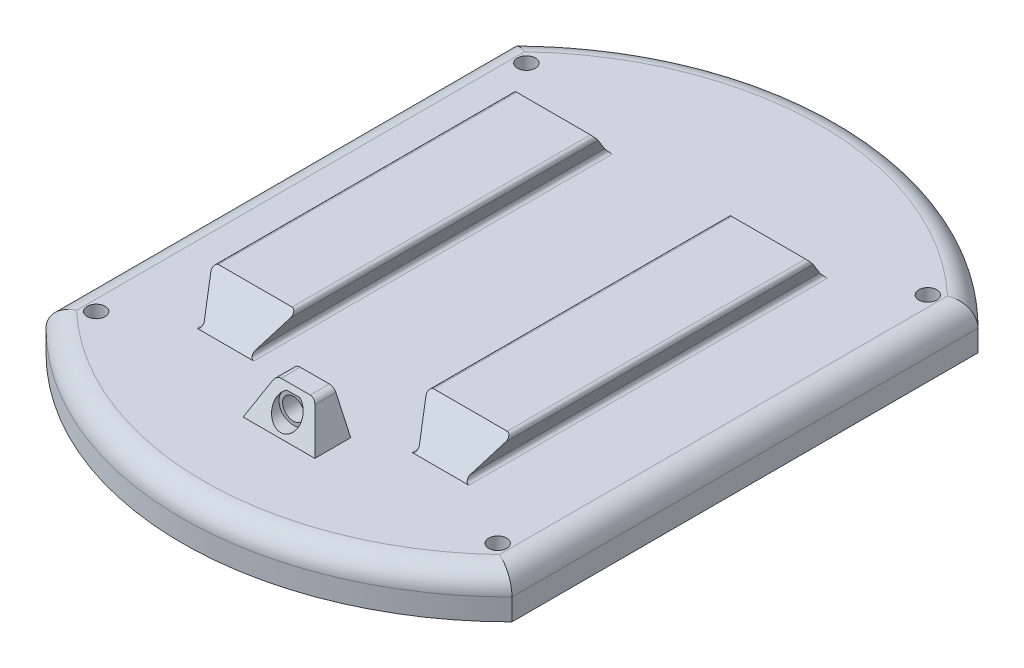
SolidWorks part; units mm, degrees
ref_plane "Спереди" through (0, 0, 0) normal (0, 0, 1) x (1, 0, 0)
ref_plane "Сверху" through (0, 0, 0) normal (0, 1, 0) x (1, 0, 0)
ref_plane "Справа" through (0, 0, 0) normal (1, 0, 0) x (0, 0, -1)
sketch "Эскиз1" plane through (0, 0, 0) normal (0, 1, 0) x (1, 0, 0)
  line L2 (0, -1000) -> (0, 49000) construction
  line L9 (-32.5, -32.5) -> (32.5, -32.5)
  line L10 (-32.5, -32.5) -> (-32.5, 32.5)
  line L11 (-32.5, 32.5) -> (32.5, 32.5)
  line L12 (32.5, -32.5) -> (32.5, 32.5)
  line L13 (-32.5, -32.5) -> (32.5, 32.5) construction
  line L14 (-32.5, 32.5) -> (32.5, -32.5) construction
  arc A5 (32.5, 32.5) -> (-32.5, 32.5) centre (0, 0.1296) ccw
  arc A6 (-32.5, -32.5) -> (32.5, -32.5) centre (0, -0.1296) ccw
  point P17 (0, 0)
  point P26 (0, 46)
  point P28 (0, -46)
  dimension "D6" = 65
  dimension "D7" = 92
extrude "Бобышка-Вытянуть1" add sketch "Эскиз1" along normal blind 6 contours L9 L12 L11 L10 | L11 A5 | L9 A6 | L9 | L9 | L11 | L11 | L11 | L11 | L9 | L9 region at (0, 0, 0) region at (0, 0, 37.9745) region at (0, 0, -37.9745)
sketch "Эскиз2" plane through (0, 0, 0) normal (0, -1, 0) x (1, 0, 0)
  line L0 (-25.75, 31.299) -> (-28, 32.5981)
  line L1 (28, 27.4019) -> (30.25, 28.701)
  line L2 (30.25, 28.701) -> (30.25, 31.299)
  line L3 (30.25, 31.299) -> (28, 32.5981)
  line L4 (28, 32.5981) -> (25.75, 31.299)
  line L5 (25.75, 31.299) -> (25.75, 28.701)
  line L6 (25.75, 28.701) -> (28, 27.4019)
  line L7 (-28, 32.5981) -> (-30.25, 31.299)
  line L8 (-30.25, 31.299) -> (-30.25, 28.701)
  line L9 (-30.25, 28.701) -> (-28, 27.4019)
  line L10 (-28, 27.4019) -> (-25.75, 28.701)
  line L11 (-25.75, 28.701) -> (-25.75, 31.299)
  line L12 (-25.75, -28.701) -> (-28, -27.4019)
  line L13 (-28, -27.4019) -> (-30.25, -28.701)
  line L14 (-30.25, -28.701) -> (-30.25, -31.299)
  line L15 (-30.25, -31.299) -> (-28, -32.5981)
  line L16 (-28, -32.5981) -> (-25.75, -31.299)
  line L17 (-25.75, -31.299) -> (-25.75, -28.701)
  line L18 (30.25, -28.701) -> (28, -27.4019)
  line L19 (28, -27.4019) -> (25.75, -28.701)
  line L20 (25.75, -28.701) -> (25.75, -31.299)
  line L21 (25.75, -31.299) -> (28, -32.5981)
  line L22 (28, -32.5981) -> (30.25, -31.299)
  line L23 (30.25, -31.299) -> (30.25, -28.701)
  circle A0 centre (28, 30) radius 2.25 construction
  circle A1 centre (-28, -30) radius 2.5981
  dimension "D1" = 4.5
  dimension "D4" = 28
  dimension "D5" = 30
  dimension "D6" = 28
  dimension "D7" = 30
  dimension "D2" = 2
  dimension "D3" = 2
extrude "Вырез-Вытянуть1" cut sketch "Эскиз2" against normal blind 3 contours L22 L23 L18 L19 L20 L21 | L5 L6 L1 L2 L3 L4 | L10 L11 L0 L7 L8 L9 | L16 L17 L12 L13 L14 L15 | L12 L13 L14 L15 L16 L17 region at (-28, 0, 30) region at (28, 0, 30) region at (-28, 0, -30) region at (28, 0, -30)
sketch "Эскиз3" plane through (0, 6, 0) normal (0, 1, 0) x (1, 0, 0)
  line L0 (-22.5, 28.0659) -> (-22.5, -28.0659)
  line L1 (22.5, -28.0659) -> (22.5, 28.0659)
  line L2 (-32.5, 32.5) -> (-32.5, -32.5)
  line L3 (32.5, -32.5) -> (32.5, 32.5)
  line L4 (-32.5, 32.5) -> (-32.5, -32.5)
  line L5 (32.5, -32.5) -> (32.5, 32.5)
  arc A0 (22.5, 28.0659) -> (-22.5, 28.0659) centre (0, 0.1296) ccw
  arc A1 (-22.5, -28.0659) -> (22.5, -28.0659) centre (0, -0.1296) ccw
  arc A2 (-32.5, -32.5) -> (32.5, -32.5) centre (0, -0.1296) ccw
  arc A3 (32.5, 32.5) -> (-32.5, 32.5) centre (0, 0.1296) ccw
  arc A4 (-32.5, -32.5) -> (32.5, -32.5) centre (0, -0.1296) ccw
  arc A5 (32.5, 32.5) -> (-32.5, 32.5) centre (0, 0.1296) ccw
  dimension "D2" = 10
  dimension "D1" = 0
sketch "Эскиз4" plane through (0, 3, 0) normal (0, -1, 0) x (1, 0, 0)
  line L0 (28, 32.5981) -> (28, 27.4019) construction
  line L1 (28, 27.4019) -> (30.25, 28.701) construction
  line L2 (-32.5, 32.5) -> (-32.5, -32.5)
  line L3 (32.5, -32.5) -> (32.5, 32.5)
  line L4 (-32.5, 32.5) -> (-32.5, -32.5)
  line L5 (32.5, -32.5) -> (32.5, 32.5)
  line L6 (25.75, 28.701) -> (30.25, 31.299) construction
  line L8 (-25.75, -31.299) -> (-25.75, -28.701) construction
  line L9 (-25.75, -30) -> (-28, -30)
  circle A0 centre (28, 30) radius 1.25
  circle A1 centre (-28, 30) radius 1.25
  arc A2 (-32.5, -32.5) -> (32.5, -32.5) centre (0, -0.1296) ccw
  arc A3 (32.5, 32.5) -> (-32.5, 32.5) centre (0, 0.1296) ccw
  arc A4 (-32.5, -32.5) -> (32.5, -32.5) centre (0, -0.1296) ccw
  arc A5 (32.5, 32.5) -> (-32.5, 32.5) centre (0, 0.1296) ccw
  circle A6 centre (-28, -30) radius 1.25
  circle A7 centre (28, -30) radius 1.25
  dimension "D2" = 2.5
  dimension "D1" = 0
  dimension "D3" = 2
  dimension "D4" = 2
extrude "Вырез-Вытянуть3" cut sketch "Эскиз4" against normal through all contours A0 | A1 | A7 | A6 region at (28, 3, 30) region at (-28, 3, 30) region at (-29.2146, 3, -30) region at (28, 3, -30)
sketch "Эскиз5" plane through (0, 0, 0) normal (0, 0, 1) x (1, 0, 0)
  line L0 (0, -1000) -> (0, 49000) construction
  line L1 (9, 11) -> (21, 11)
  line L2 (21, 11) -> (18.1132, 6)
  line L3 (9, 11) -> (11.8868, 6)
  line L4 (-32.5, 0) -> (32.5, 0)
  line L5 (-32.5, 6) -> (-32.5, 0)
  line L6 (32.5, 6) -> (-32.5, 6)
  line L7 (32.5, 0) -> (32.5, 6)
  line L8 (-32.5, 0) -> (32.5, 0)
  line L9 (-32.5, 6) -> (-32.5, 0)
  line L10 (32.5, 6) -> (-32.5, 6)
  line L11 (32.5, 0) -> (32.5, 6)
  line L12 (15, 11) -> (15, 6) construction
  line L13 (-9, 11) -> (-11.8868, 6)
  line L14 (-15, 11) -> (-15, 6) construction
  line L15 (-9, 11) -> (-21, 11)
  line L16 (-21, 11) -> (-18.1132, 6)
  point P13 (15, 8.5)
  dimension "D2" = 60
  dimension "D3" = 5
  dimension "D4" = 12
  dimension "D5" = 15
  dimension "D1" = 0
extrude "Бобышка-Вытянуть2" add sketch "Эскиз5" along normal mid plane 50 contours L15 L16 L10 L13 | L10 L2 L1 L3 region at (15, 8.764, 0) region at (-15, 8.764, 0)
draft "Уклон1" type of draft neutral plane draft angle 40 faces to draft 4 face at (15, 8.5, -25) face at (15, 8.5, 25) face at (-15, 8.5, -25) face at (-15, 8.5, 25) neutral plane through (0, 6, 0) neutral plane normal (0, 1, 0) parameters "D1"=40
fillet "Скругление1" radius 0.5 8 edges at (18.1132, 6, 0) (21, 11, 0) (9, 11, 0) (11.8868, 6, 0) (-11.8868, 6, 0) (-9, 11, 0) (-21, 11, 0) (-18.1132, 6, 0)
sketch "Эскиз6" plane through (0, 6, 0) normal (0, 1, 0) x (1, 0, 0)
  line L1 (-5, -32.5) -> (5, -32.5)
  line L2 (-5, -32.5) -> (-5, -27.5)
  line L3 (-5, -27.5) -> (5, -27.5)
  line L4 (5, -32.5) -> (5, -27.5)
  line L5 (-5, -32.5) -> (5, -27.5) construction
  line L6 (-5, -27.5) -> (5, -32.5) construction
  point P0 (0, -30)
  dimension "D1" = 10
  dimension "D2" = 5
  dimension "D3" = 30
extrude "Бобышка-Вытянуть3" add sketch "Эскиз6" along normal blind 5
draft "Уклон3" type of draft neutral plane draft angle 25 faces to draft 2 face at (5, 8.5, 30) face at (-5, 8.5, 30) neutral plane through (0, 6, 0) neutral plane normal (0, 1, 0) parameters "D1"=25
fillet "Скругление2" radius 1 2 edges at (2.6685, 11, 30) (-2.6685, 11, 30)
sketch "Эскиз7" plane through (0, 0, 32.5) normal (0, 0, 1) x (1, 0, 0)
  line L0 (-2.0314, 11) -> (2.0314, 11) construction
  circle A0 centre (0, 8.5) radius 1.5
  dimension "D1" = 3
  dimension "D2" = 2.5
extrude "Вырез-Вытянуть4" cut sketch "Эскиз7" against normal blind 5
sketch "Эскиз8" plane through (0, 0, 32.5) normal (0, 0, 1) x (1, 0, 0)
  circle A0 centre (0, 8.5) radius 1.5 construction
  circle A1 centre (0, 8.5) radius 1.5
  circle A2 centre (0, 8.5) radius 2
  dimension "D1" = 4
extrude "Вырез-Вытянуть5" cut sketch "Эскиз8" against normal blind 2
draft "Уклон5" type of draft neutral plane draft angle 25 faces to draft 1 face at (2, 8.5, 32.5) neutral plane through (0, 6, 0) neutral plane normal (0, 1, 0) parameters "D1"=25
fillet "Скругление3" radius 3 4 edges at (0, 6, 46) (-32.5, 6, 0) (32.5, 6, 0) (0, 6, -46)
